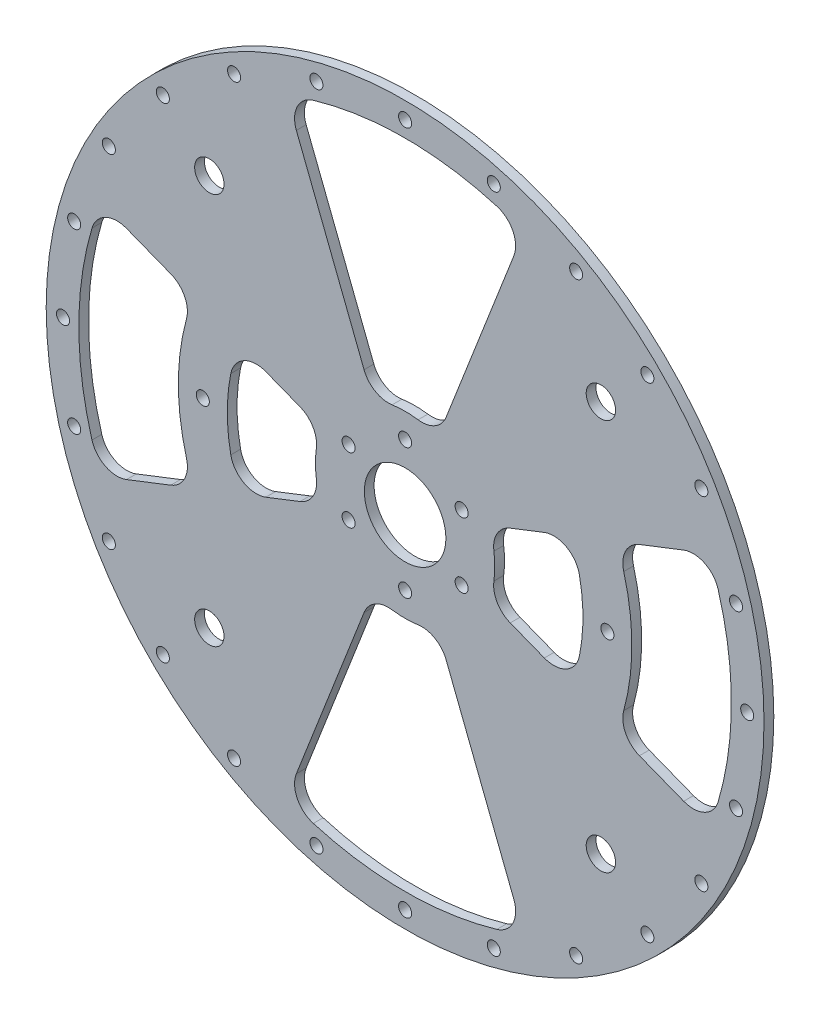
SolidWorks part; units mm, degrees
ref_plane "前视基准面" through (0, 0, 0) normal (0, 0, 1) x (1, 0, 0)
ref_plane "上视基准面" through (0, 0, 0) normal (0, 1, 0) x (1, 0, 0)
ref_plane "右视基准面" through (0, 0, 0) normal (1, 0, 0) x (0, 0, -1)
other "Configuration Table"
sketch "草图1" plane through (0, 0, 0) normal (0, 0, 1) x (1, 0, 0)
  line L13 (-60, 60) -> (0, 0) construction
  line L56 (12.577, 32.2191) -> (33.3278, 85.3771)
  line L80 (-12.577, 32.2191) -> (-33.3278, 85.3771)
  line L82 (0, 0) -> (42.0151, 0) construction
  line L84 (12.577, -32.2191) -> (33.3278, -85.3771)
  line L85 (-12.577, -32.2191) -> (-33.3278, -85.3771)
  line L90 (-85.3771, -33.3278) -> (-71.807, -28.0306)
  line L91 (-85.3771, 33.3278) -> (-71.807, 28.0306)
  line L92 (0, 0) -> (0, 20) construction
  line L93 (85.3771, -33.3278) -> (71.807, -28.0306)
  line L94 (85.3771, 33.3278) -> (71.807, 28.0306)
  line L95 (-32.2191, -12.577) -> (-42.6708, -16.657)
  line L96 (32.2191, 12.577) -> (42.6708, 16.657)
  line L97 (-32.2191, 12.577) -> (-42.6708, 16.657)
  line L98 (32.2191, -12.577) -> (42.6708, -16.657)
  circle A136 centre (0, 0) radius 110
  circle A139 centre (52.42, 90.7941) radius 2
  circle A141 centre (90.7941, 52.42) radius 2
  circle A143 centre (104.84, 0) radius 2
  circle A145 centre (90.7941, -52.42) radius 2
  circle A147 centre (52.42, -90.7941) radius 2
  circle A149 centre (0, -104.84) radius 2
  circle A151 centre (-52.42, -90.7941) radius 2
  circle A153 centre (-90.7941, -52.42) radius 2
  circle A155 centre (-104.84, 0) radius 2
  circle A157 centre (-90.7941, 52.42) radius 2
  circle A159 centre (-52.42, 90.7941) radius 2
  circle A173 centre (0, 0) radius 12.5
  circle A174 centre (0, 20) radius 2
  circle A175 centre (17.3205, 10) radius 2
  circle A176 centre (17.3205, -10) radius 2
  circle A177 centre (0, -20) radius 2
  circle A178 centre (-17.3205, -10) radius 2
  circle A179 centre (-17.3205, 10) radius 2
  circle A180 centre (-27.176, -101.4222) radius 2
  circle A181 centre (-74.2462, -74.2462) radius 2
  circle A182 centre (-101.4222, -27.176) radius 2
  circle A183 centre (-101.4222, 27.176) radius 2
  circle A184 centre (-74.2462, 74.2462) radius 2
  circle A185 centre (-27.176, 101.4222) radius 2
  circle A186 centre (27.176, 101.4222) radius 2
  circle A187 centre (74.2462, 74.2462) radius 2
  circle A188 centre (101.4222, 27.176) radius 2
  circle A189 centre (101.4222, -27.176) radius 2
  circle A190 centre (74.2462, -74.2462) radius 2
  circle A191 centre (27.176, -101.4222) radius 2
  circle A229 centre (-60, 60) radius 4.5
  circle A230 centre (60, 60) radius 4.5
  circle A231 centre (60, -60) radius 4.5
  circle A232 centre (-60, -60) radius 4.5
  circle A234 centre (-62, 0) radius 2
  circle A235 centre (62, 0) radius 2
  arc A238 (-3.9698, 27.212) -> (3.9698, 27.212) centre (0, 0) cw
  arc A240 (-28.1255, 95.9633) -> (28.1255, 95.9633) centre (0, 0) cw
  arc A242 (12.577, 32.2191) -> (3.9698, 27.212) centre (5.1247, 35.1282) cw
  arc A243 (-12.577, 32.2191) -> (-3.9698, 27.212) centre (-5.1247, 35.1282) ccw
  arc A244 (33.3278, 85.3771) -> (28.1255, 95.9633) centre (25.8755, 88.2862) ccw
  arc A245 (-33.3278, 85.3771) -> (-28.1255, 95.9633) centre (-25.8755, 88.2862) cw
  arc A246 (33.3278, -85.3771) -> (28.1255, -95.9633) centre (25.8755, -88.2862) cw
  arc A247 (12.577, -32.2191) -> (3.9698, -27.212) centre (5.1247, -35.1282) ccw
  arc A248 (-3.9698, -27.212) -> (3.9698, -27.212) centre (0, 0) ccw
  arc A249 (-12.577, -32.2191) -> (-3.9698, -27.212) centre (-5.1247, -35.1282) cw
  arc A250 (-28.1255, -95.9633) -> (28.1255, -95.9633) centre (0, 0) ccw
  arc A251 (-33.3278, -85.3771) -> (-28.1255, -95.9633) centre (-25.8755, -88.2862) ccw
  circle A253 centre (0, 104.84) radius 2
  arc A255 (-85.3771, 33.3278) -> (-95.9633, 28.1255) centre (-88.2862, 25.8755) ccw
  arc A256 (-85.3771, -33.3278) -> (-95.9633, -28.1255) centre (-88.2862, -25.8755) cw
  arc A258 (-67.0032, -18.454) -> (-67.0032, 18.454) centre (0, 0) cw
  arc A259 (-95.9633, 28.1255) -> (-95.9633, -28.1255) centre (0, 0) ccw
  arc A260 (-67.0032, -18.454) -> (-71.807, -28.0306) centre (-74.7161, -20.5782) cw
  arc A261 (-67.0032, 18.454) -> (-71.807, 28.0306) centre (-74.7161, 20.5782) ccw
  arc A262 (95.9633, 28.1255) -> (95.9633, -28.1255) centre (0, 0) cw
  arc A263 (85.3771, -33.3278) -> (95.9633, -28.1255) centre (88.2862, -25.8755) ccw
  arc A264 (67.0032, -18.454) -> (71.807, -28.0306) centre (74.7161, -20.5782) ccw
  arc A265 (67.0032, -18.454) -> (67.0032, 18.454) centre (0, 0) ccw
  arc A266 (67.0032, 18.454) -> (71.807, 28.0306) centre (74.7161, 20.5782) cw
  arc A267 (85.3771, 33.3278) -> (95.9633, 28.1255) centre (88.2862, 25.8755) cw
  arc A268 (-32.2191, -12.577) -> (-27.212, -3.9698) centre (-35.1282, -5.1247) ccw
  arc A269 (-27.212, 3.9698) -> (-27.212, -3.9698) centre (0, 0) ccw
  arc A270 (-32.2191, 12.577) -> (-27.212, 3.9698) centre (-35.1282, 5.1247) cw
  arc A274 (-53.4216, 10.7882) -> (-53.4216, -10.7882) centre (0, 0) ccw
  arc A275 (-53.4216, -10.7882) -> (-42.6708, -16.657) centre (-45.5799, -9.2046) ccw
  arc A276 (-42.6708, 16.657) -> (-53.4216, 10.7882) centre (-45.5799, 9.2046) ccw
  arc A277 (42.6708, 16.657) -> (53.4216, 10.7882) centre (45.5799, 9.2046) cw
  arc A278 (53.4216, -10.7882) -> (42.6708, -16.657) centre (45.5799, -9.2046) cw
  arc A279 (53.4216, 10.7882) -> (53.4216, -10.7882) centre (0, 0) cw
  arc A280 (32.2191, 12.577) -> (27.212, 3.9698) centre (35.1282, 5.1247) ccw
  arc A281 (27.212, 3.9698) -> (27.212, -3.9698) centre (0, 0) cw
  arc A282 (32.2191, -12.577) -> (27.212, -3.9698) centre (35.1282, -5.1247) cw
  point P5 (0, 20)
  point P8 (0, 0)
  point P10 (0, -20)
  point P25 (10, 25.6174)
  point P30 (-10, 25.6174)
  point P34 (36.3636, 93.1541)
  point P37 (-36.3636, 93.1541)
  point P44 (0, 0)
  point P67 (0, 0)
  point P260 (0, 0)
  point P276 (0, 0)
  point P325 (0, 0)
  point P351 (0, 0)
  point P362 (0, 0)
  point P388 (0, 0)
  point P413 (0, 0)
  dimension "D1" = 8
  dimension "D3" = 8
  dimension "D4" = 9
  dimension "D5" = 2
  dimension "D6" = 2
  dimension "D21" = 25
  dimension "D23" = 4
  dimension "D26" = 4
  dimension "D7" = 8
  dimension "D8" = 4
  dimension "D22" = 20
  dimension "D24" = 6
  dimension "D28" = 12
extrude "凸台-拉伸1" add sketch "草图1" along normal blind 3 contours A136 A191 A190 A189 A188 A187 A186 A185 A184 A183 A182 region at (-106.8887, 0, 0)
ref_axis "基准轴1" through (0, 0, 3) along (0, 0, -1)
